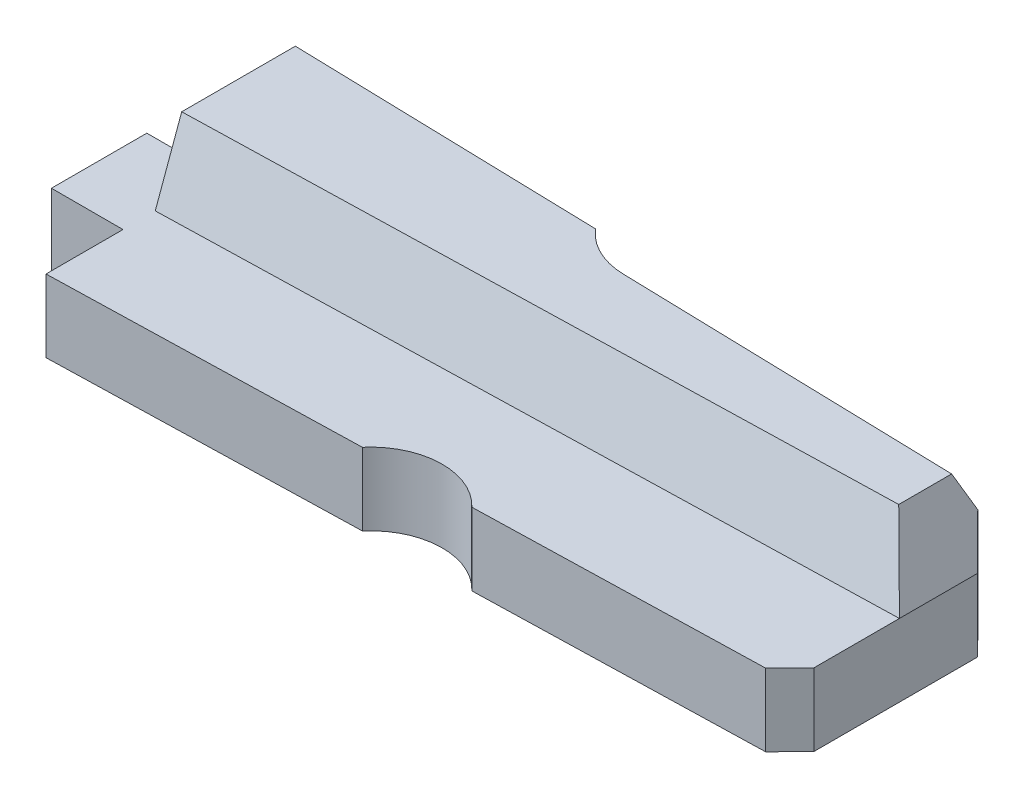
SolidWorks part; units mm, degrees
ref_plane "Front Plane" through (0, 0, 0) normal (0, 0, 1) x (1, 0, 0)
ref_plane "Top Plane" through (0, 0, 0) normal (0, 1, 0) x (1, 0, 0)
ref_plane "Right Plane" through (0, 0, 0) normal (1, 0, 0) x (0, 0, -1)
sketch "Sketch1" plane through (0, 0, 0) normal (0, 1, 0) x (1, 0, 0)
  line L0 (-14.914, 10.7961) -> (-14.914, -10.7339)
  line L1 (-14.914, -10.7339) -> (57.586, -8.8214)
  line L2 (57.586, -8.8214) -> (57.586, 8.8786)
  line L3 (57.586, 8.8786) -> (-14.914, 10.7961)
  dimension "D1" = 21.53
  dimension "D2" = 17.7
  dimension "D3" = 72.5
  dimension "D4" = 88.485
extrude "Boss-Extrude1" add sketch "Sketch1" along normal blind 6.08
sketch "Sketch2" plane through (0, 6.08, 0) normal (0, 1, 0) x (1, 0, 0)
  line L2 (-13.064, 10.7961) -> (-13.064, -10.7339)
  line L3 (-13.064, 10.7472) -> (-13.064, -1.5219)
  line L5 (-15.1556, -1.5771) -> (57.3444, 0.3354)
  line L6 (-13.064, -1.5219) -> (57.586, 0.3418)
  line L8 (57.586, 8.8786) -> (-14.914, 10.7961)
  line L9 (57.586, 8.8786) -> (-13.064, 10.7472)
  line L11 (57.586, -8.8214) -> (57.586, 8.8786)
  line L12 (57.586, 0.3418) -> (57.586, 8.8786)
  dimension "D1" = 1.85
  dimension "D2" = 9.16
  dimension "D3" = 0
  dimension "D4" = 0
extrude "Boss-Extrude2" add sketch "Sketch2" along normal blind 6.09
ref_plane "Plane1" through (0.0789, 1.0895, 2.9922) normal (0.0248, 0.342, 0.9394) x (0.9997, 0, -0.0264)
ref_axis "Axis1" through (-13.064, 12.17, -0.6954) along (0.9997, 0, -0.0264)
sketch "Sketch4" plane through (0.0789, 1.0895, 2.9922) normal (0.0248, 0.342, 0.9394) x (0.9997, 0, -0.0264)
  line L2 (-13.0996, 5.3108) -> (57.5749, 5.3108)
  line L3 (-13.0996, 5.3108) -> (57.8001, 5.3108)
  line L5 (-13.0996, 11.0335) -> (-13.0996, 5.3108)
  line L6 (-13.0996, 14.6247) -> (-13.0996, 5.3108)
  line L7 (-13.0996, 14.6247) -> (57.8001, 14.6247)
  line L10 (57.8001, 13.9523) -> (57.8001, 2.5162) construction
  line L11 (57.8001, 13.9523) -> (57.8001, 2.5162)
  line L12 (57.8001, 14.6247) -> (57.8001, 5.3108)
  dimension "D1" = 0
  dimension "D2" = 0
  dimension "D3" = 0
extrude "Cut-Extrude4" cut sketch "Sketch4" along normal blind 13.09 contours L3 L12 L7 L6
ref_plane "Plane2" through (52.8037, 19.219, 0) normal (0.9397, 0.342, 0) x (0, 0, -1)
sketch "Sketch5" plane through (52.8037, 19.219, 0) normal (0.9397, 0.342, 0) x (0, 0, -1)
  line L1 (-14.2418, -13.9822) -> (-14.2418, -1.7479)
  line L2 (-8.8214, -13.9822) -> (0.3418, -13.9822)
  line L3 (-14.2418, -13.9822) -> (15.0642, -13.9822)
  line L4 (-14.2418, -1.7479) -> (15.0642, -1.7479)
  line L5 (15.0642, -1.7479) -> (15.0642, -13.9822)
  dimension "D1" = 0
extrude "Cut-Extrude5" cut sketch "Sketch5" along normal blind 19.09
sketch "Sketch6" plane through (0, 0, 0) normal (0, -1, 0) x (1, 0, 0)
  line L0 (-14.914, 10.7339) -> (-14.914, 8.7339)
  line L1 (-14.914, -10.7961) -> (-14.914, 10.7339) construction
  line L2 (-14.914, 8.7339) -> (-12.914, 10.6811)
  line L3 (-14.914, 10.7339) -> (57.586, 8.8214) construction
  line L4 (-12.914, 10.6811) -> (-14.914, 10.7339)
  line L5 (-14.914, -10.7961) -> (-12.914, -10.7432)
  line L6 (57.586, -8.8786) -> (-14.914, -10.7961) construction
  line L7 (-12.914, -10.7432) -> (-14.914, -8.7961)
  line L8 (-14.914, -8.7961) -> (-14.914, -10.7961)
  line L9 (55.5866, 8.8741) -> (57.586, 8.8214)
  line L10 (57.586, 8.8214) -> (57.586, 6.8214)
  line L11 (57.586, 8.8214) -> (57.586, -8.8786) construction
  line L12 (57.586, 6.8214) -> (55.5866, 8.8741)
  line L13 (57.586, -8.8786) -> (57.586, -6.8786)
  line L14 (57.586, -6.8786) -> (55.586, -8.9315)
  line L15 (55.586, -8.9315) -> (57.586, -8.8786)
  line L16 (27.216, 19.304) -> (27.216, -14.3897) construction
  circle A1 centre (27.216, 13.6239) radius 6
  circle A2 centre (27.216, -13.6832) radius 6
  dimension "D11" = 12
  dimension "D12" = 12
  dimension "D1" = 2
  dimension "D2" = 2
  dimension "D3" = 2
  dimension "D4" = 2
  dimension "D5" = 2
  dimension "D6" = 2
  dimension "D7" = 2
  dimension "D8" = 2
  dimension "D9" = 42.13
  dimension "D10" = 4
  dimension "D13" = 4
extrude "Cut-Extrude6" cut sketch "Sketch6" against normal through all
ref_plane "Plane3" through (0, 7.78, 0) normal (0, 1, 0) x (1, 0, 0)
ref_axis "Axis2" through (360.074, 7.78, -0.8784) along (-0.9997, 0, -0.0264)
ref_plane "Plane4" through (0.3053, 5.2601, -11.542) normal (0.0241, 0.4146, -0.9097) x (-0.9997, 0.01, -0.0219)
sketch "Sketch7" plane through (0.3053, 5.2601, -11.542) normal (0.0241, 0.4146, -0.9097) x (-0.9997, 0.01, -0.0219)
  line L0 (-26.9217, 7.8879) -> (-26.9217, 3.0644)
  line L1 (-359.8729, 6.7147) -> (-60.2731, 3.43) construction
  line L2 (-26.9217, 3.0644) -> (-63.5754, 3.4662)
  line L3 (-63.5754, 3.4662) -> (-63.5754, 10.3897)
  line L4 (-63.5754, 10.3897) -> (-26.9217, 9.9878)
  line L5 (-26.9217, 9.9878) -> (-26.9217, 7.8879)
  ellipse E0 centre (-26.7871, 5.3996) end of major axis (-20.7874, 5.3339) minor radius 2.4875 (-22.297, 7.0089) -> (-31.2408, 7.1069) ccw construction
extrude "Cut-Extrude7" cut sketch "Sketch7" along normal blind 11.09
ref_plane "Cut surface" through (-3.214, 0, 0) normal (-1, 0, 0) x (0, 0, 1)
sketch "Sketch10" plane through (-3.214, 0, 0) normal (-1, 0, 0) x (0, 0, 1)
  line L1 (-17.6293, 15.2246) -> (18.4681, 15.2246)
  line L2 (-17.6293, 15.2246) -> (-17.6293, -7.7626)
  line L3 (-17.6293, -7.7626) -> (18.4681, -7.7626)
  line L4 (18.4681, 15.2246) -> (18.4681, -7.7626)
extrude "Cut-Extrude11" cut sketch "Sketch10" along normal through all
sketch "Sketch12" plane through (-3.214, 0, 0) normal (-1, 0, 0) x (0, 0, 1)
  line L1 (-4.0307, 6.08) -> (3.9693, 6.08)
  line L2 (-4.0307, 6.08) -> (-4.0307, 0)
  line L3 (-4.0307, 0) -> (3.9693, 0)
  line L4 (3.9693, 6.08) -> (3.9693, 0)
  line L5 (-10.4867, 0) -> (10.4253, 0) construction
  line L6 (-0.0307, -3.669) -> (-0.0307, 11.8159) construction
  line L8 (1.2621, 6.08) -> (10.4253, 6.08) construction
  line L11 (-10.4867, 12.17) -> (-10.4867, 0) construction
  line L12 (10.4253, 0) -> (10.4253, 6.08) construction
  dimension "D1" = 8
  dimension "D4" = 0
extrude "Boss-Extrude4" add sketch "Sketch12" along normal blind 6
